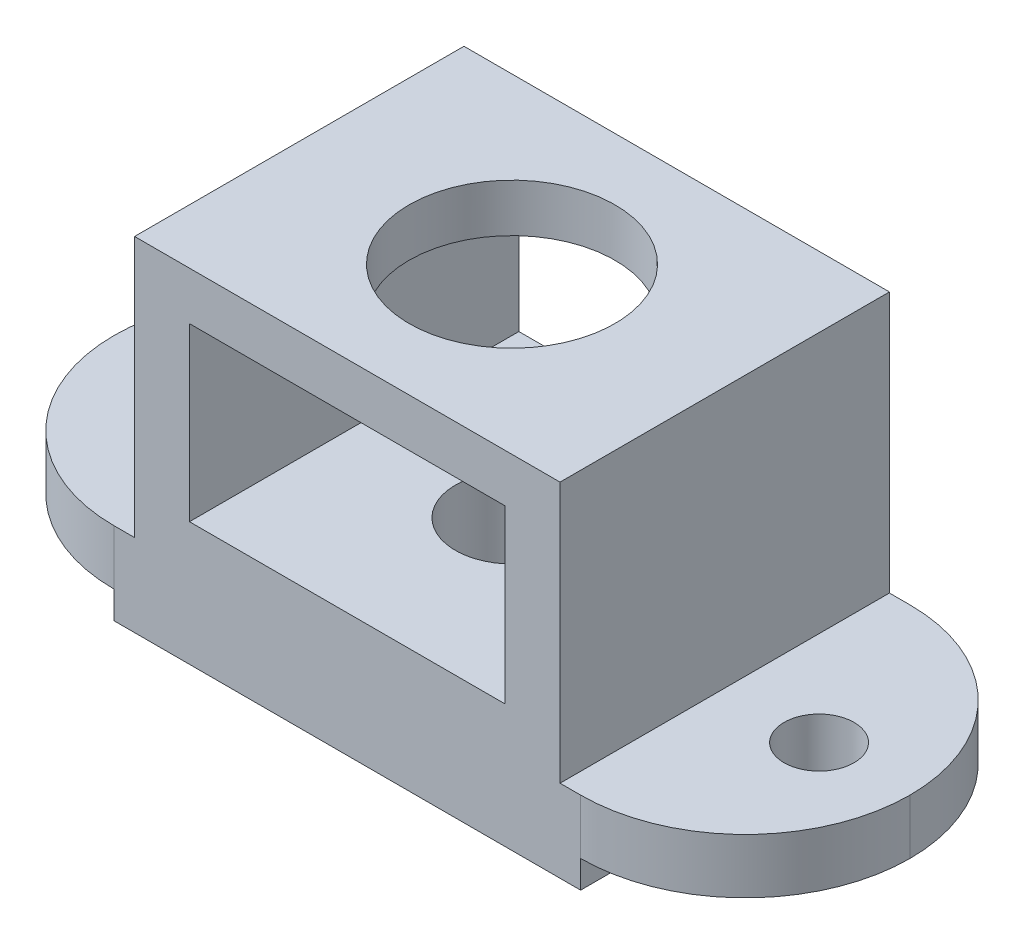
SolidWorks part; units mm, degrees
ref_plane "Спереди" through (0, 0, 0) normal (0, 0, 1) x (1, 0, 0)
ref_plane "Сверху" through (0, 0, 0) normal (0, 1, 0) x (1, 0, 0)
ref_plane "Справа" through (0, 0, 0) normal (1, 0, 0) x (0, 0, -1)
sketch "Эскиз1" plane through (0, 0, 0) normal (0, 0, 1) x (1, 0, 0)
  line L0 (0, 0) -> (24, 0)
  line L1 (24, 0) -> (24, -4)
  line L2 (24, -4) -> (92, -4)
  line L3 (92, -4) -> (92, 0)
  line L4 (92, 0) -> (116, 0)
  line L5 (116, 0) -> (116, 8)
  line L6 (116, 8) -> (89, 8)
  line L7 (89, 8) -> (89, 46)
  line L8 (89, 46) -> (27, 46)
  line L9 (27, 46) -> (27, 8)
  line L10 (0, 0) -> (0, 8)
  line L11 (0, 8) -> (27, 8)
  dimension "D1" = 24
  dimension "D2" = 27
  dimension "D3" = 38
  dimension "D4" = 4
  dimension "D5" = 8
  dimension "D6" = 50
  dimension "D7" = 68
  dimension "D8" = 62
  dimension "D9" = 38
extrude "Бобышка-Вытянуть1" add sketch "Эскиз1" along normal blind 48
fillet "Скругление1" radius 24 1 edges at (0, 4, 48) type face fillet first side face at (0, 4, 24) second side face at (58, 9.6667, 48)
fillet "Скругление2" radius 24 1 edges at (0, 4, 0) type face fillet first side face at (0, 4, 12) second side face at (58, 9.6667, 0)
fillet "Скругление3" radius 24 1 edges at (116, 4, 0) type face fillet first side face at (116, 4, 24) second side face at (65.4545, 10.5455, 0)
fillet "Скругление4" radius 24 1 edges at (116, 4, 48) type face fillet first side face at (116, 4, 36) second side face at (65.4545, 10.5455, 48)
sketch "Эскиз8" plane through (0, 0, 48) normal (0, 0, 1) x (1, 0, 0)
  line L0 (27, 46) -> (27, 8) construction
  line L1 (35, 14) -> (81, 14)
  line L2 (35, 14) -> (35, 39)
  line L3 (35, 39) -> (81, 39)
  line L4 (81, 14) -> (81, 39)
  line L5 (24, -4) -> (92, -4) construction
  dimension "D1" = 46
  dimension "D2" = 25
  dimension "D3" = 8
  dimension "D4" = 18
extrude "Вырез-Вытянуть2" cut sketch "Эскиз8" against normal through all
sketch "Эскиз9" plane through (0, -4, 0) normal (0, -1, 0) x (1, 0, 0)
  circle A0 centre (12.7433, 24) radius 5.1
  circle A1 centre (102.7433, 24) radius 5.1
  dimension "D1" = 10.2
  dimension "D2" = 10.2
  dimension "D3" = 90
extrude "Вырез-Вытянуть3" cut sketch "Эскиз9" against normal blind 48
sketch "Эскиз11" plane through (0, -4, 0) normal (0, -1, 0) x (1, 0, 0)
  circle A0 centre (58, 24) radius 8.25
  dimension "D1" = 16.5
extrude "Вырез-Вытянуть4" cut sketch "Эскиз11" against normal up to surface (18 mm away) up to face at (58, 14, 24)
sketch "Эскиз12" plane through (0, 46, 0) normal (0, 1, 0) x (1, 0, 0)
  circle A0 centre (58, -24) radius 15
  dimension "D1" = 30
extrude "Вырез-Вытянуть5" cut sketch "Эскиз12" against normal up to surface (7 mm away) up to face at (58, 39, 24)
